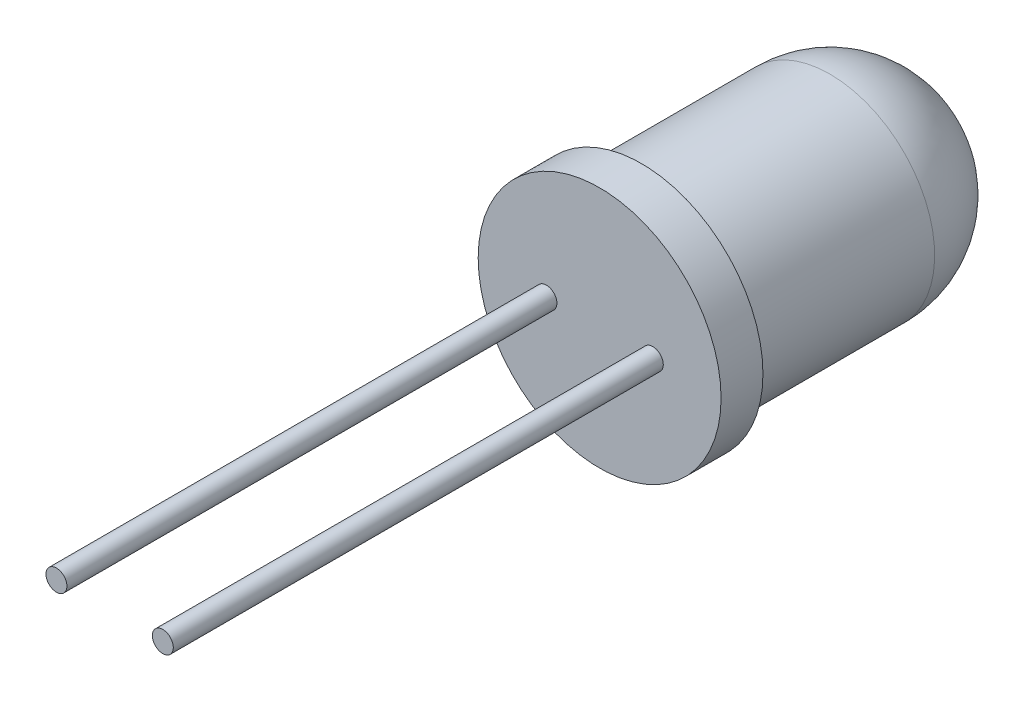
SolidWorks part; units mm, degrees
ref_plane "前视基准面" through (0, 0, 0) normal (0, 0, 1) x (1, 0, 0)
ref_plane "上视基准面" through (0, 0, 0) normal (0, 1, 0) x (1, 0, 0)
ref_plane "右视基准面" through (0, 0, 0) normal (1, 0, 0) x (0, 0, -1)
sketch "草图1" plane through (0, 0, 0) normal (0, 0, 1) x (1, 0, 0)
  circle A0 centre (0, 0) radius 2.5
  dimension "D1" = 5
extrude "拉伸1" add sketch "草图1" along normal blind 5.5
sketch "草图2" plane through (0, 0, 5.5) normal (0, 0, 1) x (1, 0, 0)
  circle A0 centre (0, 0) radius 2.9
  dimension "D1" = 5.8
extrude "拉伸2" add sketch "草图2" against normal blind 1
sketch "草图3" plane through (0, 0, 4.5) normal (0, 0, -1) x (-1, 0, 0)
  line L0 (0, 2.011) -> (0, -2.1052) construction
  line L1 (-2.1813, 0) -> (2.3335, 0) construction
  circle A0 centre (-1.27, 0) radius 0.25
  circle A1 centre (1.27, 0) radius 0.25
  dimension "D1" = 0.5
  dimension "D2" = 2.54
extrude "拉伸3" add sketch "草图3" against normal blind 12.7
sketch "草图5" plane through (0, 0, 0) normal (1, 0, 0) x (0, 0, -1)
  line L0 (0, 2.5) -> (0, 0)
  line L1 (2.5, 0) -> (0, 0)
  arc A0 (0, 2.5) -> (2.5, 0) centre (0, 0) cw
  dimension "D1" = 2.5
revolve "旋转2" add sketch "草图5" angle 360 about L1
